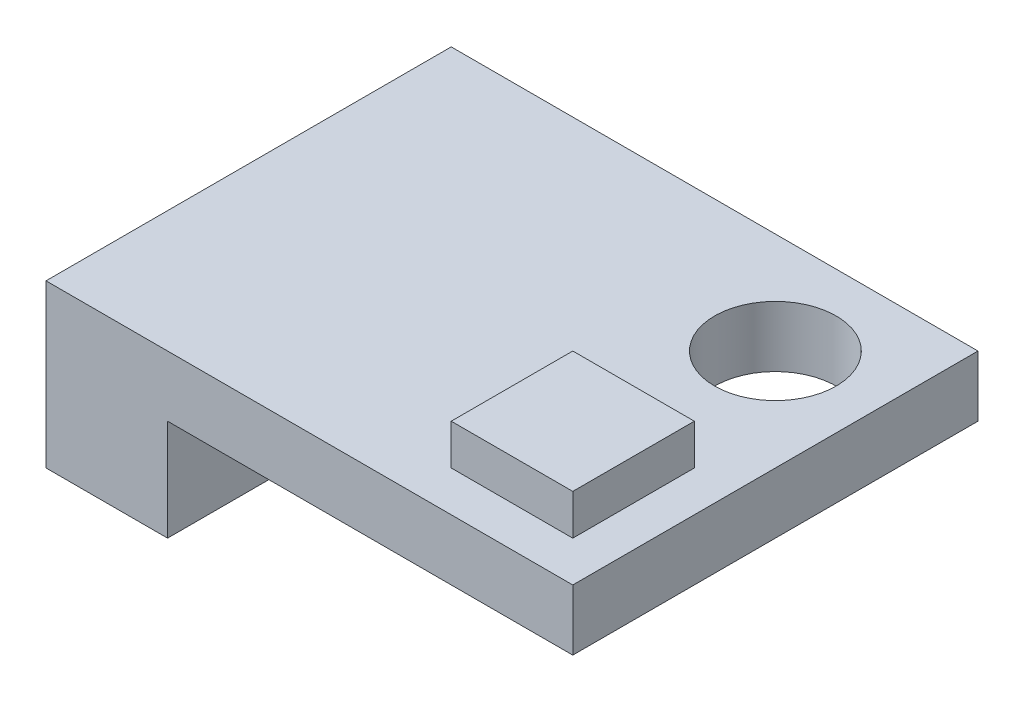
SolidWorks part; units mm, degrees
ref_plane "Спереди" through (0, 0, 0) normal (0, 0, 1) x (1, 0, 0)
ref_plane "Сверху" through (0, 0, 0) normal (0, 1, 0) x (1, 0, 0)
ref_plane "Справа" through (0, 0, 0) normal (1, 0, 0) x (0, 0, -1)
sketch "Эскиз1" plane through (0, 0, 0) normal (0, 1, 0) x (1, 0, 0)
  line L0 (6.5, 0) -> (1.5, -5) construction
  line L1 (6.5, 5) -> (-6.5, 5)
  line L2 (6.5, 5) -> (6.5, -5)
  line L3 (6.5, -5) -> (-6.5, -5)
  line L4 (-6.5, 5) -> (-6.5, -5)
  line L5 (6.5, 5) -> (-6.5, -5) construction
  line L6 (6.5, -5) -> (-6.5, 5) construction
  line L7 (6.5, -5) -> (1.5, -5) construction
  line L8 (6.5, -5) -> (6.5, 0) construction
  line L9 (6.5, 0) -> (1.5, 0) construction
  line L10 (1.5, -5) -> (1.5, 0) construction
  line L12 (5.5, -1) -> (2.5, -1)
  line L13 (5.5, -1) -> (5.5, -4)
  line L14 (5.5, -4) -> (2.5, -4)
  line L15 (2.5, -1) -> (2.5, -4)
  line L16 (5.5, -1) -> (2.5, -4) construction
  line L17 (5.5, -4) -> (2.5, -1) construction
  line L18 (6.5, 5) -> (4, 5) construction
  line L19 (6.5, 5) -> (6.5, 2.5) construction
  line L20 (6.5, 2.5) -> (4, 2.5) construction
  line L21 (4, 5) -> (4, 2.5) construction
  line L22 (-6.5, 5) -> (-3.5, 5)
  line L23 (-6.5, 5) -> (-6.5, -5)
  line L24 (-6.5, -5) -> (-3.5, -5)
  line L25 (-3.5, 5) -> (-3.5, -5)
  circle A0 centre (4, 2.5) radius 1.5
  point P0 (0, 0)
  point P9 (4, -2.5)
  dimension "D6" = 3
  dimension "D1" = 13
  dimension "D2" = 10
  dimension "D3" = 5
  dimension "D4" = 3
  dimension "D5" = 2.5
  dimension "D7" = 3
extrude "Бобышка-Вытянуть1" add sketch "Эскиз1" along normal blind 1.5 contours L25 L1 L4 L3 | L1 L25 L3 L2 A0 L15 L12 L13 L14 | L12 L15 L14 L13 region at (1.0214, 0, -0.0575) region at (-5, 0, 0) region at (4, 0, 2.5)
extrude "Бобышка-Вытянуть2" add sketch "Эскиз1<3>" against normal blind 2.5 contours L25 L1 L4 L3 region at (-5, 0, 0)
sketch "Эскиз1<3>" plane through (0, 0, 0) normal (0, 1, 0) x (1, 0, 0) same geometry as "Эскиз1"
extrude "Бобышка-Вытянуть3" add sketch "Эскиз1<4>" along normal blind 1 from surface contours L12 L15 L14 L13 region at (4, 0, 2.5) starting at face at (0, 1.5, 0)
sketch "Эскиз1<4>" plane through (0, 0, 0) normal (0, 1, 0) x (1, 0, 0) same geometry as "Эскиз1"
